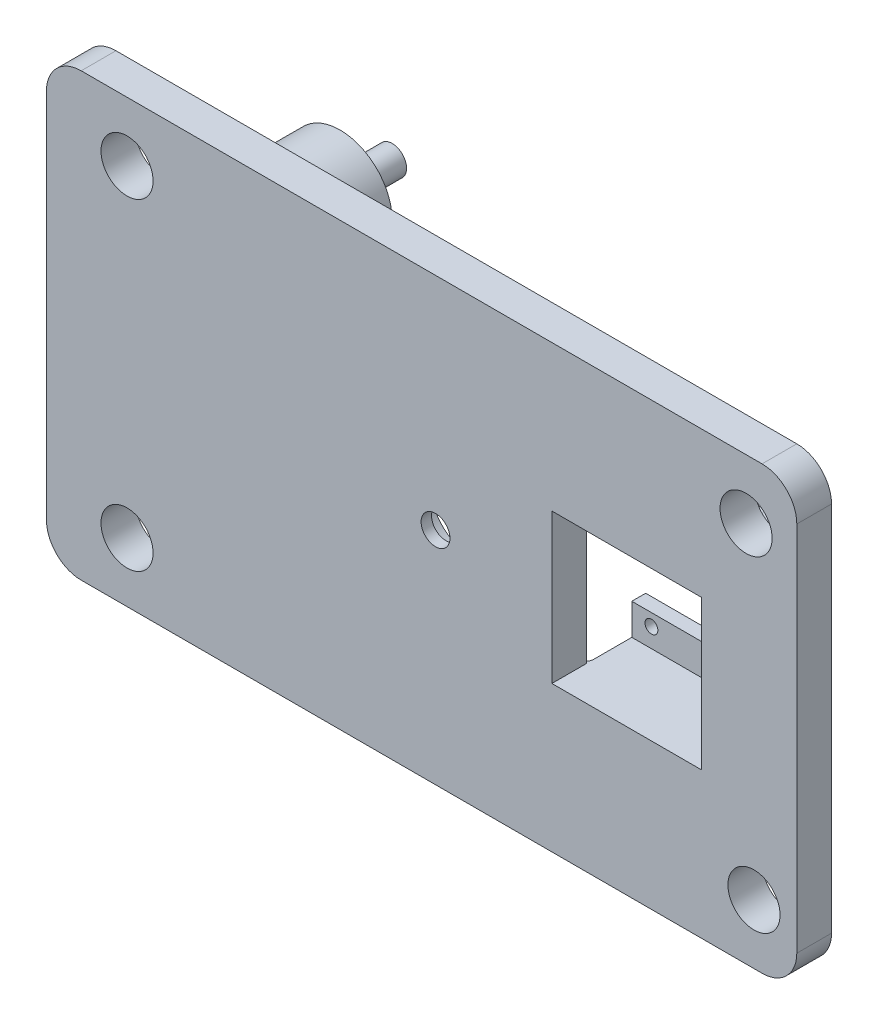
SolidWorks part; units mm, degrees
ref_plane "Front Plane" through (0, 0, 0) normal (0, 0, 1) x (1, 0, 0)
ref_plane "Top Plane" through (0, 0, 0) normal (0, 1, 0) x (1, 0, 0)
ref_plane "Right Plane" through (0, 0, 0) normal (1, 0, 0) x (0, 0, -1)
sketch "Sketch1" plane through (0, 0, 0) normal (0, 0, 1) x (1, 0, 0)
  line L1 (-108, 63.5) -> (108, 63.5)
  line L2 (-108, 63.5) -> (-108, -63.5)
  line L3 (-108, -63.5) -> (108, -63.5)
  line L4 (108, 63.5) -> (108, -63.5)
  line L5 (-108, 63.5) -> (108, -63.5) construction
  line L6 (-108, -63.5) -> (108, 63.5) construction
  point P0 (0, 0)
  dimension "D1" = 127
  dimension "D2" = 216
extrude "Boss-Extrude1" add sketch "Sketch1" along normal blind 10
fillet "Fillet1" radius 10 1 edges at (-108, 63.5, 5)
fillet "Fillet2" radius 10 3 edges at (-108, -63.5, 5) (108, 63.5, 5) (108, -63.5, 5)
sketch "Sketch9" plane through (0, 0, 0) normal (0, 0, -1) x (-1, 0, 0)
  line L0 (-98, 63.5) -> (98, 63.5) construction
  line L1 (-37.5, -21.5) -> (-80.5, -21.5)
  line L2 (-37.5, -21.5) -> (-37.5, 21.5)
  line L3 (-37.5, 21.5) -> (-80.5, 21.5)
  line L4 (-80.5, -21.5) -> (-80.5, 21.5)
  line L5 (-37.5, -21.5) -> (-80.5, 21.5) construction
  line L6 (-37.5, 21.5) -> (-80.5, -21.5) construction
  line L8 (108, 0) -> (-108, 0) construction
  line L9 (108, 53.5) -> (108, -53.5) construction
  line L10 (-108, -53.5) -> (-108, 53.5) construction
  circle A0 centre (-4, 0) radius 11.35
  point P2 (-59, 0)
  dimension "D6" = 22.7
  dimension "D1" = 27.5
  dimension "D2" = 55
  dimension "D3" = 43
  dimension "D4" = 43
  dimension "D5" = 63.5
extrude "Cut-Extrude4" cut sketch "Sketch9" against normal blind 7 contours A0
sketch "Sketch12" plane through (0, 0, 7) normal (0, 0, -1) x (-1, 0, 0)
  circle A0 centre (-4, 0) radius 4.15
  dimension "D1" = 8.3
extrude "Cut-Extrude5" cut sketch "Sketch12" against normal blind 7
extrude "Cut-Extrude6" cut sketch "Sketch9<4>" against normal through all contours L3 L4 L1 L2
sketch "Sketch9<4>" plane through (0, 0, 0) normal (0, 0, -1) x (-1, 0, 0) same geometry as "Sketch9"
sketch "Sketch13" plane through (0, 0, 0) normal (0, 0, -1) x (-1, 0, 0)
  line L1 (-37.5, -21.5) -> (-80.5, -21.5)
  line L2 (-37.5, -21.5) -> (-37.5, -25.5)
  line L3 (-37.5, -25.5) -> (-80.5, -25.5)
  line L4 (-80.5, -21.5) -> (-80.5, -25.5)
  dimension "D1" = 4
  dimension "D2" = 43
extrude "Boss-Extrude2" add sketch "Sketch13" along normal blind 17
ref_plane "Plane3" through (0, -21.5, 0) normal (0, 1, 0) x (1, 0, 0)
ref_plane "Plane4" through (0, 0, 0) normal (0, 0, -1) x (-1, 0, 0)
ref_plane "Plane6" through (80.5, 0, 0) normal (1, 0, 0) x (0, 0, -1)
sketch "Sketch16" plane through (80.5, 0, 0) normal (1, 0, 0) x (0, 0, -1)
  line L0 (17, -21.5) -> (0, -21.5) construction
  line L1 (17.0075, -21.5) -> (0.1109, -21.5)
  line L2 (17.0075, -21.5) -> (17.0075, -25.5)
  line L3 (17.0075, -25.5) -> (0.1109, -25.5)
  line L4 (0.1109, -21.5) -> (0.1109, -25.5)
  line L5 (17, -25.5) -> (0, -25.5) construction
fillet "Fillet4" radius 2 3 edges at (59, -25.5, 0) (37.5, -23.5, 0) (80.5, -23.5, 0)
sketch "Sketch17" plane through (0, -21.5, 0) normal (0, 1, 0) x (1, 0, 0)
  line L0 (80.5, 17.0075) -> (80.5, 0.1109) construction
  line L1 (37.5, 17) -> (80.5, 17)
  line L2 (37.5, 17) -> (37.5, 13)
  line L3 (37.5, 13) -> (80.5, 13)
  line L4 (80.5, 17) -> (80.5, 13)
  dimension "D1" = 4
extrude "Boss-Extrude5" add sketch "Sketch17" along normal blind 9
sketch "Sketch18" plane through (0, 0, 0) normal (0, 0, -1) x (-1, 0, 0)
  line L1 (-37.5, 21.5) -> (-80.5, 21.5)
  line L2 (-37.5, 21.5) -> (-37.5, 25.5)
  line L3 (-37.5, 25.5) -> (-80.5, 25.5)
  line L4 (-80.5, 21.5) -> (-80.5, 25.5)
  dimension "D1" = 43
  dimension "D2" = 4
extrude "Boss-Extrude6" add sketch "Sketch18" along normal blind 17
ref_plane "Plane7" through (0, 21.5, 0) normal (0, -1, 0) x (-1, 0, 0)
sketch "Sketch19" plane through (0, 21.5, 0) normal (0, -1, 0) x (-1, 0, 0)
  line L0 (-80.5, 17) -> (-80.5, 0) construction
  line L1 (-37.5, 17) -> (-80.5, 17)
  line L2 (-37.5, 17) -> (-37.5, 13)
  line L3 (-37.5, 13) -> (-80.5, 13)
  line L4 (-80.5, 17) -> (-80.5, 13)
  dimension "D1" = 4
extrude "Boss-Extrude7" add sketch "Sketch19" along normal blind 9
fillet "Fillet5" radius 2 3 edges at (37.5, 23.5, 0) (80.5, 23.5, 0) (59, 25.5, 0)
ref_plane "Plane8" through (0, 0, -17) normal (0, 0, -1) x (-1, 0, 0)
sketch "Sketch20" plane through (0, 0, -17) normal (0, 0, -1) x (-1, 0, 0)
  line L0 (-37.5, -25.5) -> (-37.5, -12.5) construction
  line L2 (-80.5, -21.5) -> (-37.5, -21.5)
  line L3 (-80.5, -12.5) -> (-80.5, -25.5) construction
  line L4 (-80.5, -12.5) -> (-37.5, -12.5) construction
  circle A0 centre (-43.15, -16) radius 1.85
  circle A1 centre (-74.85, -16) radius 1.85
  dimension "D3" = 5.5
  dimension "D4" = 3.7
  dimension "D5" = 5.65
  dimension "D6" = 3.7
  dimension "D1" = 5.65
  dimension "D2" = 9
extrude "Cut-Extrude7" cut sketch "Sketch20" against normal blind 9 contours A1 | A0
ref_plane "Plane9" through (0, 0, -17) normal (0, 0, -1) x (-1, 0, 0)
sketch "Sketch23" plane through (0, 0, -17) normal (0, 0, -1) x (-1, 0, 0)
  line L0 (-37.5, 21.5) -> (-80.5, 21.5)
  line L1 (-37.5, 12.5) -> (-37.5, 25.5) construction
  line L2 (-80.5, 25.5) -> (-80.5, 12.5) construction
  line L3 (-37.5, 12.5) -> (-80.5, 12.5) construction
  circle A0 centre (-43.15, 15.85) radius 1.85
  circle A1 centre (-74.85, 16) radius 1.85
  dimension "D4" = 3.7
  dimension "D5" = 3.7
  dimension "D6" = 5.65
  dimension "D7" = 5.65
  dimension "D1" = 9
  dimension "D2" = 5.5
  dimension "D3" = 5.65
extrude "Cut-Extrude8" cut sketch "Sketch23" against normal blind 9 contours A0 | A1
ref_plane "Plane10" through (0, 0, 0) normal (0, 0, -1) x (-1, 0, 0)
sketch "Sketch25" plane through (0, 0, 0) normal (0, 0, -1) x (-1, 0, 0)
  line L0 (5.8491, 5.5555) -> (-13.8858, -5.5762)
  line L1 (-4, -11.35) -> (-4, 11.35)
  line L2 (98, -63.5) -> (-98, -63.5) construction
  line L3 (-98, 63.5) -> (98, 63.5) construction
  circle A0 centre (5.8491, 5.5555) radius 0.0422
  circle A1 centre (-4, 0) radius 11.35 construction
  circle A2 centre (50.9816, -43.5) radius 15
  circle A3 centre (50.9816, 43.5) radius 15
  point P8 (-4.0184, -0.0104)
  dimension "D4" = 20
  dimension "D5" = 30
  dimension "D6" = 30
  dimension "D1" = 55
  dimension "D2" = 55
  dimension "D3" = 20
extrude "Boss-Extrude9" add sketch "Sketch25" along normal blind 17.5 contours A3 | A2
ref_plane "Plane11" through (0, 0, -17.5) normal (0, 0, -1) x (-1, 0, 0)
sketch "Sketch26" plane through (0, 0, -17.5) normal (0, 0, -1) x (-1, 0, 0)
  circle A0 centre (50.9816, -43.5) radius 4.15
  dimension "D1" = 8.3
extrude "Boss-Extrude10" add sketch "Sketch26" along normal blind 15
ref_plane "Plane12" through (0, 0, -17.5) normal (0, 0, -1) x (-1, 0, 0)
sketch "Sketch27" plane through (0, 0, -17.5) normal (0, 0, -1) x (-1, 0, 0)
  circle A0 centre (50.9816, 43.5) radius 4.15
  dimension "D1" = 8.3
extrude "Boss-Extrude11" add sketch "Sketch27" along normal blind 15
fillet "Fillet9" radius 2 1 edges at (-35.9816, -43.5, 0)
fillet "Fillet10" radius 2 1 edges at (-35.9816, 43.5, 0)
ref_plane "Plane13" through (0, 0, 10) normal (0, 0, 1) x (1, 0, 0)
sketch "Sketch28" plane through (0, 0, 10) normal (0, 0, 1) x (1, 0, 0)
  line L0 (98, 63.5) -> (-98, 63.5) construction
  line L3 (-98, -63.5) -> (98, -63.5) construction
  circle A0 centre (-84.8117, 46.37) radius 7.5
  circle A1 centre (-84.8117, -46.37) radius 7.5
  circle A2 centre (95.674, -46.3698) radius 7.5
  circle A3 centre (93.3991, 46.37) radius 7.5
  dimension "D2" = 15
  dimension "D3" = 17.13
  dimension "D4" = 15
  dimension "D5" = 17.13
  dimension "D6" = 15
  dimension "D7" = 15
  dimension "D1" = 17.13
extrude "Cut-Extrude9" cut sketch "Sketch28" against normal through all
